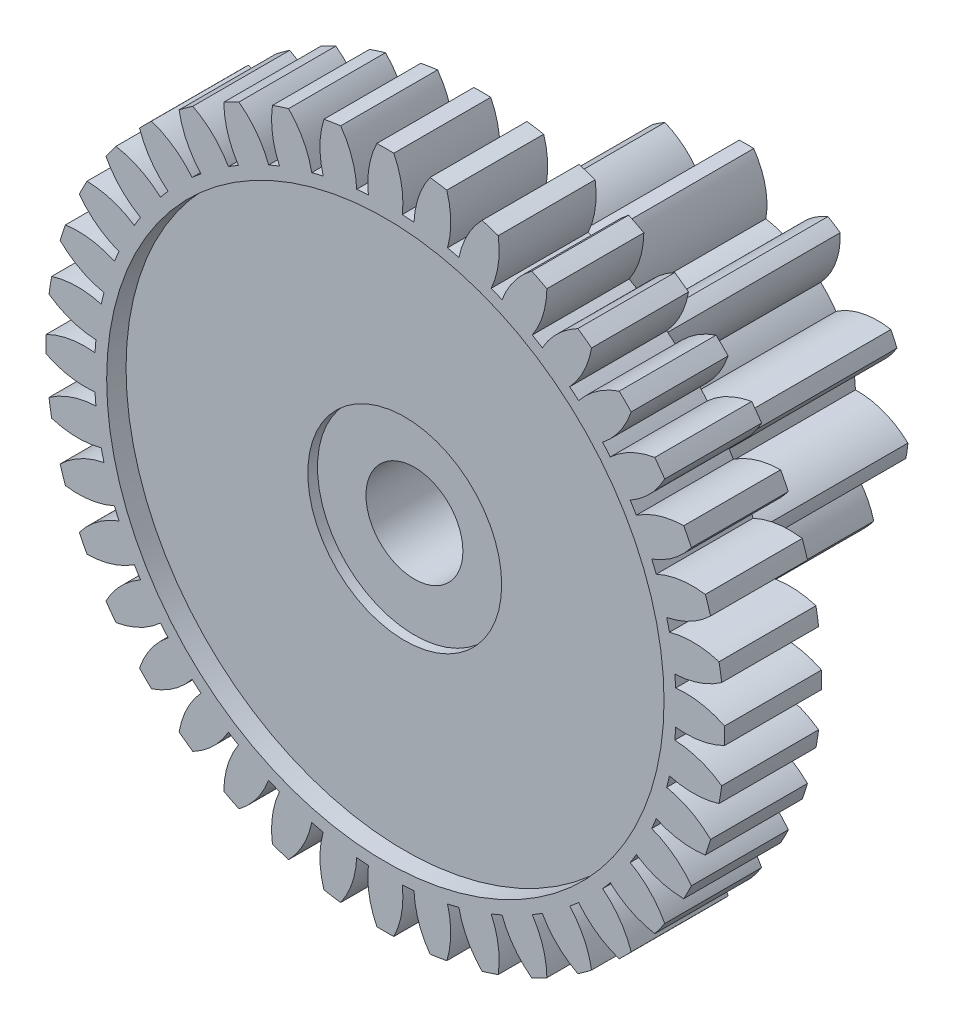
SolidWorks part; units mm, degrees
material "ABS PC"
ref_plane "Front Plane" through (0, 0, 0) normal (0, 0, 1) x (1, 0, 0)
ref_plane "Top Plane" through (0, 0, 0) normal (0, 1, 0) x (1, 0, 0)
ref_plane "Right Plane" through (0, 0, 0) normal (1, 0, 0) x (0, 0, -1)
sketch "Sketch1" plane through (0, 0, 0) normal (0, 0, 1) x (1, 0, 0)
  circle A0 centre (0, 0) radius 6
  dimension "D1" = 12
extrude "Extrude1" add sketch "Sketch1" along normal mid plane 2
sketch "Sketch2" plane through (0, 0, 0) normal (0, 0, 1) x (1, 0, 0)
  line L0 (-7, 0) -> (-6, 0) construction
  arc A2 (-5.9898, 0.35) -> (-5.9898, -0.35) centre (0, 0) ccw
  arc A3 (-6.9978, -0.175) -> (-5.9898, -0.35) centre (-6.1986, 1.4378) ccw
  arc A4 (-6.9978, 0.175) -> (-6.9978, -0.175) centre (0, 0) ccw
  arc A5 (-5.9898, 0.35) -> (-6.9978, 0.175) centre (-6.1986, -1.4378) ccw
  circle A12 centre (0, 0) radius 6 construction
  point P7 (0, 0)
  dimension "D1" = 1
  dimension "D3" = 1.8
  dimension "D4" = 0.35
  dimension "D5" = 0.7
extrude "Extrude2" add sketch "Sketch2" against normal mid plane 2
pattern_circular "CirPattern1" count 40 over 360 about axis through (0, 0, 1) along (0, 0, -1) of "Extrude2"
sketch "Sketch3" plane through (0, 0, -1) normal (0, 0, -1) x (-1, 0, 0)
  circle A0 centre (0, 0) radius 2
  circle A1 centre (0, 0) radius 5.75
  dimension "D1" = 4
  dimension "D2" = 11.5
extrude "Cut-Extrude1" cut sketch "Sketch3" against normal blind 0.4
mirror "Mirror1" about plane through (0, 0, 0) normal (0, 0, 1) of "Cut-Extrude1"
sketch "Sketch4" plane through (0, 0, -0.6) normal (0, 0, -1) x (-1, 0, 0)
  line L0 (0, 2.6) -> (0, 0) construction
  circle A0 centre (0, 0) radius 2.25
  dimension "D1" = 4.5
extrude "Extrude3" add sketch "Sketch4" along normal blind 5.85
sketch "Sketch6" plane through (0, 0, -6.45) normal (0, 0, -1) x (-1, 0, 0)
  line L0 (0, 0) -> (0, 3.3487) construction
  arc A0 (0.15, 3.3444) -> (-0.15, 3.3444) centre (0, 0.7487) ccw
  arc A1 (-0.15, 3.3444) -> (-0.4, 2.2142) centre (1.0922, 2.4768) ccw
  arc A2 (0.4, 2.2142) -> (0.15, 3.3444) centre (-1.0922, 2.4768) ccw
  circle A3 centre (0, 0) radius 2.25 construction
  circle A4 centre (0, 0) radius 2.25 construction
  arc A5 (0.4, 2.2142) -> (-0.4, 2.2142) centre (0, 0) ccw
  point P1 (0, 2.25)
  point P12 (0, 0)
  dimension "D1" = 1.5151
  dimension "D2" = 0.8
  dimension "D5" = 2.6
  dimension "D3" = 0.2999
  dimension "D4" = 1.1302
extrude "Extrude4" add sketch "Sketch6" against normal up to surface (5.85 mm away) up to face at (-5.75, 0, -0.6)
pattern_circular "CirPattern2" count 11 over 360 of "Extrude3", "Extrude4"
sketch "Sketch5" plane through (0, 0, -6.45) normal (0, 0, -1) x (-1, 0, 0)
  circle A0 centre (0, 0) radius 1
  dimension "D1" = 2
extrude "Cut-Extrude2" cut sketch "Sketch5" against normal up to surface (7.45 mm away) up to face at (0, 0, 1)
sketch "Sketch7" plane through (0, 0, 1) normal (0, 0, 1) x (1, 0, 0)
  circle A1 centre (0, 0) radius 2
  circle A2 centre (0, 0) radius 2
  dimension "D1" = 0
extrude "Cut-Extrude3" cut sketch "Sketch7" against normal blind 0.6
